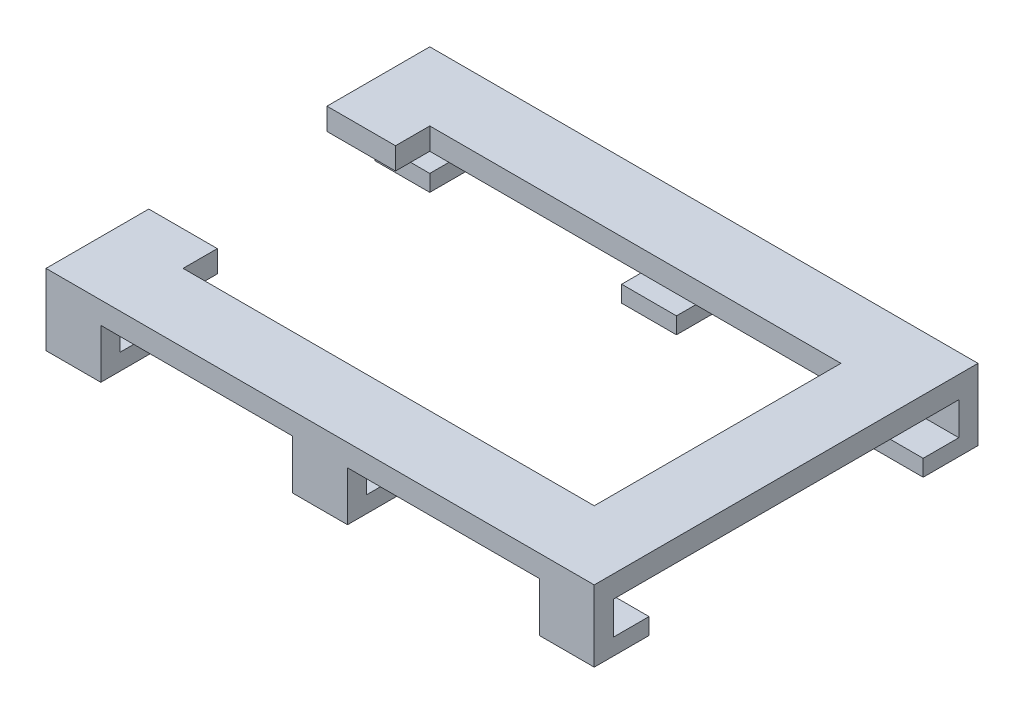
SolidWorks part; units mm, degrees
ref_plane "Alzado" through (0, 0, 0) normal (0, 0, 1) x (1, 0, 0)
ref_plane "Planta" through (0, 0, 0) normal (0, 1, 0) x (1, 0, 0)
ref_plane "Vista lateral" through (0, 0, 0) normal (1, 0, 0) x (0, 0, -1)
sketch "Croquis1" plane through (0, 0, 0) normal (0, 1, 0) x (1, 0, 0)
  line L0 (75, 45) -> (-75, 45)
  line L1 (100, -70) -> (-100, -70)
  line L2 (100, -70) -> (100, 70)
  line L3 (100, 70) -> (-100, 70)
  line L4 (-100, -70) -> (-100, 70)
  line L5 (100, -70) -> (-100, 70) construction
  line L6 (100, 70) -> (-100, -70) construction
  line L7 (-75, -45) -> (-75, 45)
  line L8 (75, -45) -> (-75, -45)
  line L9 (75, -45) -> (75, 45)
  point P0 (0, 0)
  dimension "D1" = 140
  dimension "D2" = 200
  dimension "D3" = 25
extrude "Saliente-Extruir1" add sketch "Croquis1" along normal blind 8
sketch "Croquis2" plane through (-100, 0, 0) normal (-1, 0, 0) x (0, 0, 1)
  line L0 (70, 0) -> (70, -18)
  line L1 (70, -18) -> (50, -18)
  line L2 (50, -18) -> (50, -12)
  line L3 (50, -12) -> (63, -12)
  line L4 (63, -12) -> (63, 0)
  line L5 (-70, 0) -> (70, 0) construction
  line L6 (63, 0) -> (70, 0)
  dimension "D1" = 7
  dimension "D2" = 6
  dimension "D3" = 20
  dimension "D4" = 18
extrude "Saliente-Extruir2" add sketch "Croquis2" against normal blind 20
mirror "Simetría1" about plane through (0, 0, 0) normal (1, 0, 0) of "Saliente-Extruir2"
mirror "Simetría2" about plane through (0, 0, 0) normal (0, 0, 1) of "Simetría1"
sketch "Croquis3" plane through (0, 8, 0) normal (0, 1, 0) x (1, 0, 0)
  line L1 (-120, 32.5) -> (-60, 32.5)
  line L2 (-120, 32.5) -> (-120, -32.5)
  line L3 (-120, -32.5) -> (-60, -32.5)
  line L4 (-60, 32.5) -> (-60, -32.5)
  point P4 (-60, 0)
  dimension "D1" = 65
  dimension "D2" = 60
  dimension "D3" = 60
extrude "Cortar-Extruir1" cut sketch "Croquis3" against normal through all
mirror "Simetría3" [suppressed] about plane through (0, 0, 0) normal (1, 0, 0)
sketch "Croquis4" plane through (0, 0, 0) normal (1, 0, 0) x (0, 0, -1)
  line L0 (-50, -18) -> (-70, -18) construction
  line L1 (-50, -12) -> (-50, -18) construction
  line L2 (-63, -12) -> (-50, -12) construction
  line L3 (-63, 0) -> (-63, -12) construction
  line L4 (-50, -18) -> (-70, -18)
  line L5 (-50, -12) -> (-50, -18)
  line L6 (-63, -12) -> (-50, -12)
  line L7 (-63, 0) -> (-63, -12)
  line L8 (-70, -18) -> (-70, 0)
  line L9 (-70, 0) -> (-63, 0)
extrude "Saliente-Extruir3" add sketch "Croquis4" along normal mid plane 20
mirror "Simetría4" about plane through (0, 0, 0) normal (0, 0, 1) of "Saliente-Extruir3"
